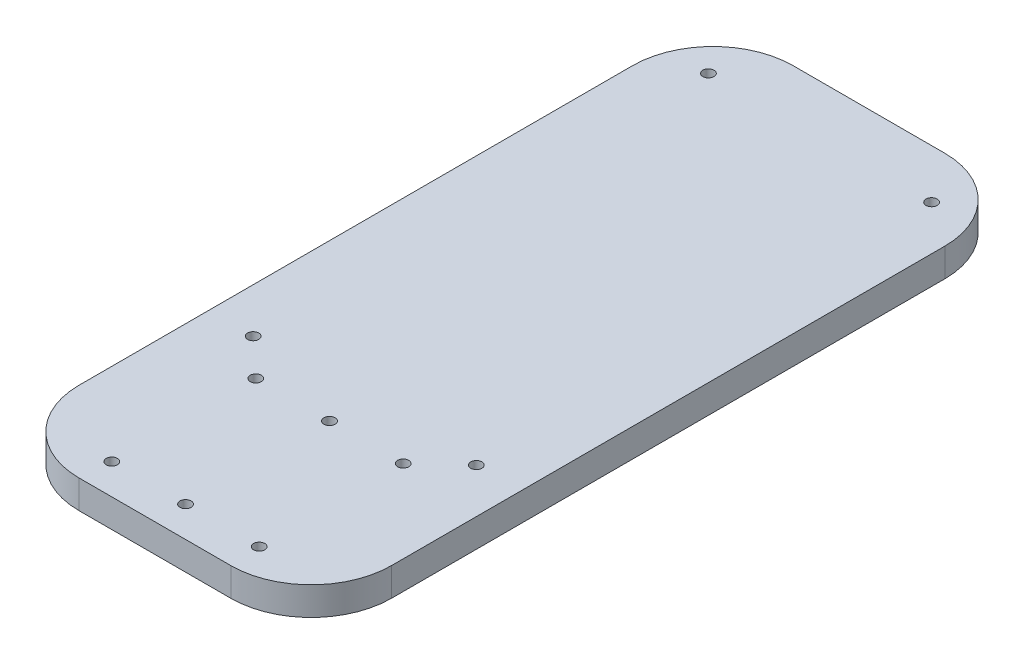
SolidWorks part; units mm, degrees
material "6061 Alloy"
ref_plane "Front Plane" through (0, 0, 0) normal (0, 0, 1) x (1, 0, 0)
ref_plane "Top Plane" through (0, 0, 0) normal (0, 1, 0) x (1, 0, 0)
ref_plane "Right Plane" through (0, 0, 0) normal (1, 0, 0) x (0, 0, -1)
sketch "Sketch1" plane through (0, 0, 0) normal (0, 1, 0) x (1, 0, 0)
  line L1 (-35, 80) -> (35, 80)
  line L2 (-35, 80) -> (-35, -80)
  line L3 (-35, -80) -> (35, -80)
  line L4 (35, 80) -> (35, -80)
  line L5 (-35, 80) -> (35, -80) construction
  line L6 (-35, -80) -> (35, 80) construction
  point P0 (0, 0)
  dimension "D1" = 160
  dimension "D2" = 70
extrude "Boss-Extrude1" add sketch "Sketch1" along normal blind 6.35
sketch "Sketch2" plane through (0, 0, 0) normal (0, 1, 0) x (1, 0, 0)
  line L0 (35, -80) -> (35, 80) construction
  line L1 (-13, 73) -> (13, 73)
  line L2 (-28, 58) -> (-28, -58)
  line L3 (-13, -73) -> (13, -73)
  line L4 (28, 58) -> (28, -58)
  line L5 (-28, 73) -> (28, -73) construction
  line L6 (-28, -73) -> (28, 73) construction
  line L7 (-35, -80) -> (35, -80) construction
  arc A0 (-28, -58) -> (-13, -73) centre (-13, -58) ccw
  arc A1 (13, -73) -> (28, -58) centre (13, -58) ccw
  arc A2 (13, 73) -> (28, 58) centre (13, 58) cw
  arc A3 (-13, 73) -> (-28, 58) centre (-13, 58) ccw
  point P0 (0, 0)
  point P18 (28, 0)
  dimension "D3" = 15
  dimension "D1" = 7
  dimension "D2" = 7
sketch "Sketch7" plane through (0, 0, 0) normal (0, 0, 1) x (1, 0, 0)
  line L0 (-28, 0) -> (28, 0) construction
  line L1 (25.6505, 0) -> (30.3495, 0)
  line L2 (25.6505, 0) -> (25.6505, 2.5)
  line L3 (25.6505, 2.5) -> (30.3495, 2.5)
  line L4 (30.3495, 0) -> (30.3495, 2.5)
  circle A0 centre (28, 0) radius 2 construction
  dimension "D1" = 4.699
  dimension "D2" = 2.5
sweep "Cut-Sweep2" cut profiles "Sketch7" path "Sketch2"
fillet "Fillet1" radius 18 4 edges at (-35, 3.175, 80) (-35, 3.175, -80) (35, 3.175, -80) (35, 3.175, 80)
sketch "Sketch11" plane through (0, 0, 0) normal (0, -1, 0) x (1, 0, 0)
  line L0 (18, -20.5118) -> (-18, 20.5118) construction
  line L1 (-16.5355, -61.5355) -> (16.5355, 61.5355) construction
  line L4 (13, 75.3495) -> (-13, 75.3495) construction
  line L5 (18, 20.5118) -> (18, -20.5118) construction
  line L6 (-13, -75.3495) -> (13, -75.3495) construction
  line L7 (-17, 80) -> (17, 80) construction
  line L8 (18, 20.5118) -> (18, 61.5355) construction
  line L9 (-35, -62) -> (-35, 62) construction
  line L10 (18, -20.5118) -> (18, -61.5355) construction
  line L11 (16.5355, -61.5355) -> (10.3455, -61.5355) construction
  line L12 (16.5355, 61.5355) -> (13.194, 61.5355) construction
  line L13 (17, -80) -> (-17, -80) construction
  line L18 (13, 63) -> (-13, 63) construction
  line L19 (-18, 58) -> (-18, -58) construction
  line L21 (-13, -63) -> (13, -63) construction
  line L22 (18, -58) -> (18, -20.5118) construction
  line L23 (18, -20.5118) -> (18, 58) construction
  line L24 (0, 75.3495) -> (0, -75.3495) construction
  circle A5 centre (16.5355, 61.5355) radius 1.65
  circle A8 centre (18, -20.5118) radius 1.65
  circle A9 centre (18, 20.5118) radius 1.65
  circle A10 centre (-16.5355, 61.5355) radius 1.65
  circle A11 centre (-18, 20.5118) radius 1.65
  circle A16 centre (16.5355, -61.5355) radius 1.65
  arc A18 (-13, 63) -> (-18, 58) centre (-13, 58) ccw construction
  arc A19 (-18, -58) -> (-13, -63) centre (-13, -58) ccw construction
  arc A20 (13, -63) -> (18, -58) centre (13, -58) ccw construction
  arc A21 (18, 58) -> (13, 63) centre (13, 58) ccw construction
  circle A22 centre (-18, -20.5118) radius 1.65
  circle A23 centre (-16.5355, -61.5355) radius 1.65
  point P39 (0, 0)
  dimension "D2" = 3.3
  dimension "D1" = 17
  dimension "D3" = 41.0237
  dimension "D4" = 41.0237
  dimension "D5" = 41.0237
  dimension "D6" = 17
  dimension "D7" = 17
extrude "Cut-Extrude4" cut sketch "Sketch11" against normal blind 3.5
sketch "Sketch12" [suppressed] plane through (-393.4497, 13.2196, 0) normal (0, -1, 0) x (1, 0, 0)
  circle A2 centre (376.9142, -61.5355) radius 2.1
  circle A3 centre (411.4497, 20.5118) radius 1.65
  circle A4 centre (411.4497, 20.5118) radius 1.65 construction
  circle A5 centre (411.4497, -20.5118) radius 1.65
  circle A6 centre (411.4497, -20.5118) radius 1.65 construction
  circle A7 centre (376.9142, 61.5355) radius 1.65
  circle A8 centre (376.9142, 61.5355) radius 1.65 construction
  circle A9 centre (409.9852, 61.5355) radius 1.65
  circle A10 centre (409.9852, 61.5355) radius 1.65 construction
  circle A11 centre (376.9142, -61.5355) radius 1.65
  circle A12 centre (376.9142, -61.5355) radius 1.65 construction
  circle A13 centre (375.4497, -20.5118) radius 1.65
  circle A14 centre (375.4497, -20.5118) radius 1.65 construction
  circle A15 centre (409.9852, -61.5355) radius 1.65
  circle A16 centre (409.9852, -61.5355) radius 1.65 construction
  circle A17 centre (375.4497, 20.5118) radius 1.65
  circle A29 centre (375.4497, 20.5118) radius 1.65 construction
  circle A30 centre (409.9852, -61.5355) radius 2.1
  circle A31 centre (411.4497, -20.5118) radius 2.1
  circle A32 centre (375.4497, -20.5118) radius 2.1
  circle A33 centre (375.4497, 20.5118) radius 2.1
  circle A34 centre (376.9142, 61.5355) radius 2.1
  circle A35 centre (409.9852, 61.5355) radius 2.1
  circle A36 centre (411.4497, 20.5118) radius 2.1
  dimension "D9" = 4.2
  dimension "D1" = 0
  dimension "D2" = 0
  dimension "D3" = 0
  dimension "D4" = 0
  dimension "D5" = 0
  dimension "D6" = 0
  dimension "D7" = 0
  dimension "D8" = 0
extrude "Cut-Extrude5" [suppressed] cut sketch "Sketch12" along normal through all
sketch "Sketch13" [suppressed] plane through (0, 0, 0) normal (0, -1, 0) x (1, 0, 0)
  line L0 (-22.5355, -61.5355) -> (-22.5355, -26.5118)
  line L1 (22.5355, 61.5355) -> (22.5355, -61.5355)
  line L2 (16.5355, -67.5355) -> (-21.5355, -67.5355)
  line L3 (-16.5355, 67.5355) -> (16.5355, 67.5355)
  line L4 (-10.5355, 61.5355) -> (-10.5355, 67.5355)
  line L5 (-16.5355, 55.5355) -> (-22.5355, 55.5355)
  line L6 (16.5355, 55.5355) -> (22.5355, 55.5355)
  line L7 (10.5355, 61.5355) -> (10.5355, 67.5355)
  line L8 (-18, -14.5118) -> (-22.5355, -14.5118)
  line L9 (-18, -26.5118) -> (-22.5355, -26.5118)
  line L10 (-22.5355, -14.5118) -> (-22.5355, 61.5355)
  line L11 (-18, 14.5118) -> (-22.5355, 14.5118)
  line L12 (-18, 26.5118) -> (-22.5355, 26.5118)
  line L13 (18, 14.5118) -> (22.5355, 14.5118)
  line L14 (18, 26.5118) -> (22.5355, 26.5118)
  line L15 (18, -14.5118) -> (22.5355, -14.5118)
  line L16 (18, -26.5118) -> (22.7855, -26.5118)
  line L17 (16.5355, -55.5355) -> (22.5355, -55.5355)
  line L18 (10.5355, -61.5355) -> (10.5355, -67.5355)
  line L19 (-10.5355, -61.5355) -> (-10.5355, -67.5355)
  line L20 (-16.5355, -55.5355) -> (-22.5355, -55.5355)
  line L22 (35, 62) -> (35, -62) construction
  line L23 (-35, -62) -> (-35, 62) construction
  line L24 (17, -80) -> (-17, -80) construction
  line L25 (-17, 80) -> (17, 80) construction
  circle A0 centre (18, 20.5118) radius 6
  circle A2 centre (18, 20.5118) radius 2.25 construction
  circle A4 centre (16.5355, 61.5355) radius 2.25 construction
  circle A8 centre (18, -20.5118) radius 2.25 construction
  circle A10 centre (-18, 20.5118) radius 3.1018 construction
  circle A12 centre (-16.5355, 61.5355) radius 2.25 construction
  circle A14 centre (-18, -20.5118) radius 2.25 construction
  circle A16 centre (-16.5355, -61.5355) radius 2.25 construction
  circle A17 centre (16.5355, 61.5355) radius 6
  circle A18 centre (-16.5355, 61.5355) radius 6
  circle A19 centre (18, -20.5118) radius 6
  circle A20 centre (-18, 20.5118) radius 6
  circle A21 centre (16.5355, -61.5355) radius 6
  arc A22 (-18, -26.5118) -> (-18, -14.5118) centre (-18, -20.5118) ccw
  circle A23 centre (-16.5355, -61.5355) radius 6
  dimension "D1" = 12
  dimension "D2" = 12.4645
  dimension "D7" = 6
  dimension "D4" = 12.4645
  dimension "D5" = 12.4645
  dimension "D6" = 12.4645
extrude "Cut-Extrude6" [suppressed] cut sketch "Sketch13" against normal through all contours A23 L19 L2 L18 A21 L17 L1 L16 A19 L15 L13 A0 L14 L6 A17 L7 L3 L4 A18 L5 L10 L12 A20 L11 L8 A22 L9 L0 L20
fillet "Fillet2" [suppressed] radius 12
chamfer "Chamfer1" [suppressed] distance 1 angle 45
fillet "Fillet5" [suppressed] radius 1
sketch "Sketch14" plane through (0, 6.35, 0) normal (0, 1, 0) x (1, 0, 0)
  line L3 (-18.161, -38.6021) -> (-18.161, -40.8881)
  line L4 (-14.859, -40.8881) -> (-14.859, -38.6021)
  line L5 (-14.859, -38.6021) -> (-18.161, -38.6021)
  line L6 (-18.161, -38.6021) -> (-18.161, -40.8881) construction
  line L7 (-14.859, -40.8881) -> (-14.859, -38.6021) construction
  line L8 (-14.859, -38.6021) -> (-18.161, -38.6021) construction
  line L9 (-1.651, -38.6021) -> (-1.651, -40.8881)
  line L10 (1.651, -40.8881) -> (1.651, -38.6021)
  line L11 (1.651, -38.6021) -> (-1.651, -38.6021)
  line L12 (-1.651, -38.6021) -> (-1.651, -40.8881) construction
  line L13 (1.651, -40.8881) -> (1.651, -38.6021) construction
  line L14 (1.651, -38.6021) -> (-1.651, -38.6021) construction
  line L15 (14.859, -38.6021) -> (14.859, -40.8881)
  line L16 (18.161, -40.8881) -> (18.161, -38.6021)
  line L17 (18.161, -38.6021) -> (14.859, -38.6021)
  line L18 (14.859, -38.6021) -> (14.859, -40.8881) construction
  line L19 (18.161, -40.8881) -> (18.161, -38.6021) construction
  line L20 (18.161, -38.6021) -> (14.859, -38.6021) construction
  line L21 (-1.651, -75.4321) -> (1.651, -75.4321)
  line L22 (-1.651, -73.1461) -> (-1.651, -75.4321)
  line L23 (1.651, -75.4321) -> (1.651, -73.1461)
  line L24 (-1.651, -75.4321) -> (1.651, -75.4321) construction
  line L25 (-1.651, -73.1461) -> (-1.651, -75.4321) construction
  line L26 (1.651, -75.4321) -> (1.651, -73.1461) construction
  line L27 (-18.161, -75.4321) -> (-14.859, -75.4321)
  line L28 (-18.161, -73.1461) -> (-18.161, -75.4321)
  line L29 (-14.859, -75.4321) -> (-14.859, -73.1461)
  line L30 (-18.161, -75.4321) -> (-14.859, -75.4321) construction
  line L31 (-18.161, -73.1461) -> (-18.161, -75.4321) construction
  line L32 (-14.859, -75.4321) -> (-14.859, -73.1461) construction
  line L33 (14.859, -75.4321) -> (18.161, -75.4321)
  line L34 (14.859, -73.1461) -> (14.859, -75.4321)
  line L35 (18.161, -75.4321) -> (18.161, -73.1461)
  line L36 (14.859, -75.4321) -> (18.161, -75.4321) construction
  line L37 (14.859, -73.1461) -> (14.859, -75.4321) construction
  line L38 (18.161, -75.4321) -> (18.161, -73.1461) construction
  circle A0 centre (-16.51, -40.8881) radius 1.25
  circle A1 centre (-26.25, 51.5127) radius 1.375
  circle A2 centre (-26.25, 51.5127) radius 1.375 construction
  circle A3 centre (-26.25, 42.5127) radius 1.375
  circle A4 centre (-26.25, 42.5127) radius 1.375 construction
  circle A5 centre (-26.25, 33.5127) radius 1.375
  circle A6 centre (-26.25, 33.5127) radius 1.375 construction
  circle A7 centre (-26.25, 15.0127) radius 1.375
  circle A8 centre (-26.25, 15.0127) radius 1.375 construction
  circle A9 centre (-25, -32.9873) radius 1.625
  circle A10 centre (-25, -32.9873) radius 1.625 construction
  circle A11 centre (25, -32.9873) radius 1.625
  circle A12 centre (25, -32.9873) radius 1.625 construction
  circle A13 centre (25, 69.0127) radius 1.625
  circle A14 centre (25, 69.0127) radius 1.625 construction
  circle A15 centre (-25, 69.0127) radius 1.625
  circle A16 centre (-25, 69.0127) radius 1.625 construction
  circle A17 centre (-26.25, 24.0127) radius 1.375
  circle A18 centre (-26.25, 24.0127) radius 1.375 construction
  circle A19 centre (-26.25, 60.5127) radius 1.375
  circle A20 centre (-26.25, 60.5127) radius 1.375 construction
  arc A21 (-18.161, -40.8881) -> (-14.859, -40.8881) centre (-16.51, -40.8881) ccw
  arc A22 (-18.161, -40.8881) -> (-14.859, -40.8881) centre (-16.51, -40.8881) ccw construction
  arc A23 (-1.651, -40.8881) -> (1.651, -40.8881) centre (0, -40.8881) ccw
  arc A24 (-1.651, -40.8881) -> (1.651, -40.8881) centre (0, -40.8881) ccw construction
  arc A25 (14.859, -40.8881) -> (18.161, -40.8881) centre (16.51, -40.8881) ccw
  arc A26 (14.859, -40.8881) -> (18.161, -40.8881) centre (16.51, -40.8881) ccw construction
  arc A27 (1.651, -73.1461) -> (-1.651, -73.1461) centre (0, -73.1461) ccw
  arc A28 (1.651, -73.1461) -> (-1.651, -73.1461) centre (0, -73.1461) ccw construction
  arc A29 (-14.859, -73.1461) -> (-18.161, -73.1461) centre (-16.51, -73.1461) ccw
  arc A30 (-14.859, -73.1461) -> (-18.161, -73.1461) centre (-16.51, -73.1461) ccw construction
  arc A31 (18.161, -73.1461) -> (14.859, -73.1461) centre (16.51, -73.1461) ccw
  arc A32 (18.161, -73.1461) -> (14.859, -73.1461) centre (16.51, -73.1461) ccw construction
  circle A33 centre (0, -40.8881) radius 1.25
  circle A34 centre (16.51, -40.8881) radius 1.25
  circle A35 centre (16.51, -73.1461) radius 1.25
  circle A36 centre (0, -73.1461) radius 1.25
  circle A37 centre (-16.51, -73.1461) radius 1.25
  circle A38 centre (-25, -32.9873) radius 1.25
  circle A39 centre (25, -32.9873) radius 1.25
  circle A40 centre (25, 69.0127) radius 1.25
  circle A41 centre (-25, 69.0127) radius 1.25
  dimension "D17" = 2.5
  dimension "D1" = 0
  dimension "D2" = 0
  dimension "D3" = 0
  dimension "D4" = 0
  dimension "D5" = 0
  dimension "D6" = 0
  dimension "D7" = 0
  dimension "D8" = 0
  dimension "D9" = 0
  dimension "D10" = 0
  dimension "D11" = 0
  dimension "D12" = 0
  dimension "D13" = 0
  dimension "D14" = 0
  dimension "D15" = 0
  dimension "D16" = 0
extrude "Cut-Extrude7" cut sketch "Sketch14" against normal blind 3.5
equation "\"D1@Boss-Extrude1\"=.25in"
